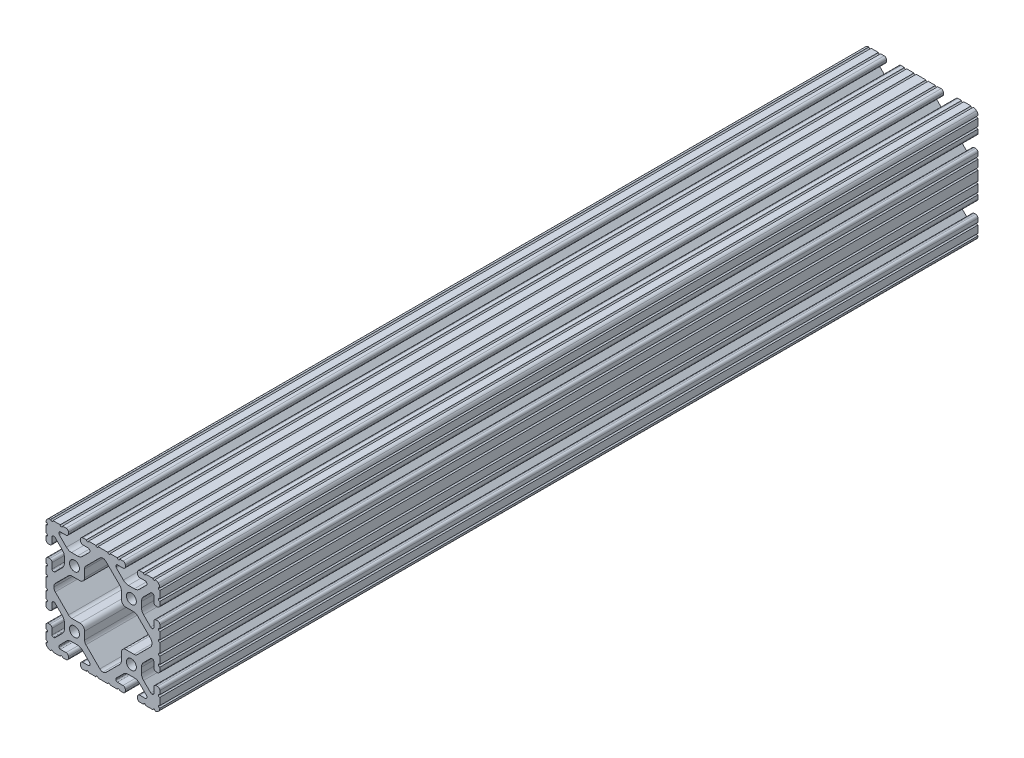
SolidWorks part; units mm, degrees
ref_plane "Front Plane" through (0, 0, 0) normal (0, 0, 1) x (1, 0, 0)
ref_plane "Top Plane" through (0, 0, 0) normal (0, 1, 0) x (1, 0, 0)
ref_plane "Right Plane" through (0, 0, 0) normal (1, 0, 0) x (0, 0, -1)
sketch "Sketch1" plane through (0, 0, 0) normal (0, 0, 1) x (1, 0, 0)
  line L0 (0, 38.1) -> (0, -38.1) construction
  line L1 (-38.1, -38.1) -> (38.1, -38.1) construction
  line L2 (-38.1, -38.1) -> (-38.1, 38.1) construction
  line L3 (-38.1, 38.1) -> (38.1, 38.1) construction
  line L4 (38.1, -38.1) -> (38.1, 38.1) construction
  line L5 (0, 38.1) -> (0, -38.1) construction
  line L6 (-38.1, 0) -> (38.1, 0) construction
  line L7 (-19.05, 19.05) -> (19.05, 19.05) construction
  line L8 (-19.05, 19.05) -> (-19.05, -19.05) construction
  line L9 (-19.05, -19.05) -> (19.05, -19.05) construction
  line L10 (19.05, 19.05) -> (19.05, -19.05) construction
  line L11 (-23.114, 38.1) -> (-23.114, -38.1) construction
  line L12 (-23.114, -38.1) -> (-14.986, 38.1) construction
  line L13 (-14.986, 38.1) -> (-14.986, -38.1) construction
  circle A0 centre (19.05, 19.05) radius 3.3274
  point P0 (0, 0)
  point P9 (0, 0)
  point P12 (-19.05, 0)
  line B0 (-11.3637, -22.8433) -> (-2.0515, -32.1555)
  line B1 (-12.2936, -15.4686) -> (-12.2936, -20.5983)
  line B2 (-20.769, -12.2936) -> (-15.4686, -12.2936)
  line B3 (-31.9021, -2.4756) -> (-23.0141, -11.3637)
  line B4 (-23.0141, 11.3637) -> (-31.9021, 2.4756)
  line B5 (-15.4686, 12.2936) -> (-20.769, 12.2936)
  line B6 (-12.2936, 20.5983) -> (-12.2936, 15.4686)
  line B7 (-2.0515, 32.1555) -> (-11.3637, 22.8433)
  line B8 (11.3637, 22.8433) -> (2.0515, 32.1555)
  line B9 (12.2936, 15.4686) -> (12.2936, 20.5983)
  line B10 (20.769, 12.2936) -> (15.4686, 12.2936)
  line B11 (31.9021, 2.4756) -> (23.0141, 11.3637)
  line B12 (23.0141, -11.3637) -> (31.9021, -2.4756)
  line B13 (15.4686, -12.2936) -> (20.769, -12.2936)
  line B14 (12.2936, -20.5983) -> (12.2936, -15.4686)
  line B15 (2.0515, -32.1555) -> (11.3637, -22.8433)
  line B16 (-4.7773, 38.1) -> (-9.6053, 38.1)
  line B17 (-11.1289, 38.1) -> (-13.4112, 38.1)
  line B18 (-14.986, 36.5252) -> (-14.986, 35.6108)
  line B19 (-13.4112, 34.036) -> (-9.652, 34.036)
  line B20 (-8.763, 33.147) -> (-8.763, 32.4935)
  line B21 (-9.0234, 31.8649) -> (-13.6907, 27.1976)
  line B22 (-17.0493, 25.8064) -> (-21.0507, 25.8064)
  line B23 (-24.4093, 27.1976) -> (-29.1002, 31.8885)
  line B24 (-29.337, 32.7207) -> (-29.337, 33.147)
  line B25 (-28.448, 34.036) -> (-24.6888, 34.036)
  line B26 (-23.114, 35.6108) -> (-23.114, 36.5252)
  line B27 (-24.6888, 38.1) -> (-27.0772, 38.1)
  line B28 (-28.6011, 38.1) -> (-33.4288, 38.1)
  line B29 (-38.1, 33.373) -> (-38.1, 28.5453)
  line B30 (-38.1, 27.0238) -> (-38.1, 24.6302)
  line B31 (-36.5252, 23.0554) -> (-35.6108, 23.0554)
  line B32 (-34.036, 24.6302) -> (-34.036, 28.448)
  line B33 (-33.147, 29.337) -> (-32.6643, 29.337)
  line B34 (-32.0357, 29.0766) -> (-27.1976, 24.2385)
  line B35 (-25.8064, 20.8799) -> (-25.8064, 17.2201)
  line B36 (-27.1976, 13.8615) -> (-31.9489, 9.1101)
  line B37 (-32.7869, 8.763) -> (-33.0603, 8.763)
  line B38 (-34.036, 9.7387) -> (-34.036, 13.4698)
  line B39 (-35.6108, 15.0446) -> (-36.5252, 15.0446)
  line B40 (-38.1, 13.4698) -> (-38.1, 11.075)
  line B41 (-38.1, 9.552) -> (-38.1, 4.7238)
  line B42 (-38.1, 3.2007) -> (-38.1, -3.2007)
  line B43 (-38.1, -4.7238) -> (-38.1, -9.552)
  line B44 (-38.1, -11.075) -> (-38.1, -13.4698)
  line B45 (-36.5252, -15.0446) -> (-35.6108, -15.0446)
  line B46 (-34.036, -13.4698) -> (-34.036, -9.7387)
  line B47 (-33.0603, -8.763) -> (-32.7869, -8.763)
  line B48 (-31.9489, -9.1101) -> (-27.1976, -13.8615)
  line B49 (-25.8064, -17.2201) -> (-25.8064, -20.8799)
  line B50 (-27.1976, -24.2385) -> (-32.0357, -29.0766)
  line B51 (-32.6643, -29.337) -> (-33.147, -29.337)
  line B52 (-34.036, -28.448) -> (-34.036, -24.6302)
  line B53 (-35.6108, -23.0554) -> (-36.5252, -23.0554)
  line B54 (-38.1, -24.6302) -> (-38.1, -27.0238)
  line B55 (-38.1, -28.5453) -> (-38.1, -33.373)
  line B56 (-33.4288, -38.1) -> (-28.6011, -38.1)
  line B57 (-27.0772, -38.1) -> (-24.6888, -38.1)
  line B58 (-23.114, -36.5252) -> (-23.114, -35.6108)
  line B59 (-24.6888, -34.036) -> (-28.448, -34.036)
  line B60 (-29.337, -33.147) -> (-29.337, -32.7207)
  line B61 (-29.1002, -31.8885) -> (-24.4093, -27.1976)
  line B62 (-21.0507, -25.8064) -> (-17.0493, -25.8064)
  line B63 (-13.6907, -27.1976) -> (-9.0234, -31.8649)
  line B64 (-8.763, -32.4935) -> (-8.763, -33.147)
  line B65 (-9.652, -34.036) -> (-13.4112, -34.036)
  line B66 (-14.986, -35.6108) -> (-14.986, -36.5252)
  line B67 (-13.4112, -38.1) -> (-11.1289, -38.1)
  line B68 (-9.6053, -38.1) -> (-4.7773, -38.1)
  line B69 (-3.2537, -38.1) -> (3.2537, -38.1)
  line B70 (4.7773, -38.1) -> (9.6053, -38.1)
  line B71 (11.1289, -38.1) -> (13.4112, -38.1)
  line B72 (14.986, -36.5252) -> (14.986, -35.6108)
  line B73 (13.4112, -34.036) -> (9.652, -34.036)
  line B74 (8.763, -33.147) -> (8.763, -32.4935)
  line B75 (9.0234, -31.8649) -> (13.6907, -27.1976)
  line B76 (17.0493, -25.8064) -> (21.0507, -25.8064)
  line B77 (24.4093, -27.1976) -> (29.1002, -31.8885)
  line B78 (29.337, -32.7207) -> (29.337, -33.147)
  line B79 (28.448, -34.036) -> (24.6888, -34.036)
  line B80 (23.114, -35.6108) -> (23.114, -36.5252)
  line B81 (24.6888, -38.1) -> (27.0772, -38.1)
  line B82 (28.6011, -38.1) -> (33.4288, -38.1)
  line B83 (38.1, -33.373) -> (38.1, -28.5453)
  line B84 (38.1, -27.0238) -> (38.1, -24.6302)
  line B85 (36.5252, -23.0554) -> (35.6108, -23.0554)
  line B86 (34.036, -24.6302) -> (34.036, -28.448)
  line B87 (33.147, -29.337) -> (32.6643, -29.337)
  line B88 (32.0357, -29.0766) -> (27.1976, -24.2385)
  line B89 (25.8064, -20.8799) -> (25.8064, -17.2201)
  line B90 (27.1976, -13.8615) -> (31.9489, -9.1101)
  line B91 (32.7869, -8.763) -> (33.0603, -8.763)
  line B92 (34.036, -9.7387) -> (34.036, -13.4698)
  line B93 (35.6108, -15.0446) -> (36.5252, -15.0446)
  line B94 (38.1, -13.4698) -> (38.1, -11.075)
  line B95 (38.1, -9.552) -> (38.1, -4.7238)
  line B96 (38.1, -3.2007) -> (38.1, 3.2007)
  line B97 (38.1, 4.7238) -> (38.1, 9.552)
  line B98 (38.1, 11.075) -> (38.1, 13.4698)
  line B99 (36.5252, 15.0446) -> (35.6108, 15.0446)
  line B100 (34.036, 13.4698) -> (34.036, 9.7387)
  line B101 (33.0603, 8.763) -> (32.7869, 8.763)
  line B102 (31.9489, 9.1101) -> (27.1976, 13.8615)
  line B103 (25.8064, 17.2201) -> (25.8064, 20.8799)
  line B104 (27.1976, 24.2385) -> (32.0357, 29.0766)
  line B105 (32.6643, 29.337) -> (33.147, 29.337)
  line B106 (34.036, 28.448) -> (34.036, 24.6302)
  line B107 (35.6108, 23.0554) -> (36.5252, 23.0554)
  line B108 (38.1, 24.6302) -> (38.1, 27.0238)
  line B109 (38.1, 28.5453) -> (38.1, 33.373)
  line B110 (33.4288, 38.1) -> (28.6011, 38.1)
  line B111 (27.0772, 38.1) -> (24.6888, 38.1)
  line B112 (23.114, 36.5252) -> (23.114, 35.6108)
  line B113 (24.6888, 34.036) -> (28.448, 34.036)
  line B114 (29.337, 33.147) -> (29.337, 32.7207)
  line B115 (29.1002, 31.8885) -> (24.4093, 27.1976)
  line B116 (21.0507, 25.8064) -> (17.0493, 25.8064)
  line B117 (13.6907, 27.1976) -> (9.0234, 31.8649)
  line B118 (8.763, 32.4935) -> (8.763, 33.147)
  line B119 (9.652, 34.036) -> (13.4112, 34.036)
  line B120 (14.986, 35.6108) -> (14.986, 36.5252)
  line B121 (13.4112, 38.1) -> (11.1289, 38.1)
  line B122 (9.6053, 38.1) -> (4.7773, 38.1)
  line B123 (3.2537, 38.1) -> (-3.2537, 38.1)
  circle B124 centre (-19.05, 19.05) radius 3.3274
  circle B125 centre (-19.05, -19.05) radius 3.3274
  circle B126 centre (19.05, -19.05) radius 3.3274
  circle B127 centre (19.05, 19.05) radius 3.3274
  arc B128 (0, -33.011) -> (2.0515, -32.1555) centre (-0.0139, -30.09) ccw
  arc B129 (-2.0515, -32.1555) -> (0, -33.011) centre (0.0139, -30.09) ccw
  arc B130 (-12.2936, -20.5983) -> (-11.3637, -22.8433) centre (-9.1186, -20.5983) ccw
  arc B131 (-12.2936, -15.4686) -> (-15.4686, -12.2936) centre (-15.4686, -15.4686) ccw
  arc B132 (-23.0141, -11.3637) -> (-20.769, -12.2936) centre (-20.769, -9.1186) ccw
  arc B133 (-32.7287, 0) -> (-31.9021, -2.4756) centre (-29.8367, -0.4102) ccw
  arc B134 (-31.9021, 2.4756) -> (-32.7287, 0) centre (-29.8367, 0.4102) ccw
  arc B135 (-20.769, 12.2936) -> (-23.0141, 11.3637) centre (-20.769, 9.1186) ccw
  arc B136 (-15.4686, 12.2936) -> (-12.2936, 15.4686) centre (-15.4686, 15.4686) ccw
  arc B137 (-11.3637, 22.8433) -> (-12.2936, 20.5983) centre (-9.1186, 20.5983) ccw
  arc B138 (0, 33.011) -> (-2.0515, 32.1555) centre (0.0139, 30.09) ccw
  arc B139 (2.0515, 32.1555) -> (0, 33.011) centre (-0.0139, 30.09) ccw
  arc B140 (12.2936, 20.5983) -> (11.3637, 22.8433) centre (9.1186, 20.5983) ccw
  arc B141 (12.2936, 15.4686) -> (15.4686, 12.2936) centre (15.4686, 15.4686) ccw
  arc B142 (23.0141, 11.3637) -> (20.769, 12.2936) centre (20.769, 9.1186) ccw
  arc B143 (32.7287, 0) -> (31.9021, 2.4756) centre (29.8367, 0.4102) ccw
  arc B144 (31.9021, -2.4756) -> (32.7287, 0) centre (29.8367, -0.4102) ccw
  arc B145 (20.769, -12.2936) -> (23.0141, -11.3637) centre (20.769, -9.1186) ccw
  arc B146 (15.4686, -12.2936) -> (12.2936, -15.4686) centre (15.4686, -15.4686) ccw
  arc B147 (11.3637, -22.8433) -> (12.2936, -20.5983) centre (9.1186, -20.5983) ccw
  arc B148 (-4.7773, 38.1) -> (-3.2537, 38.1) centre (-4.0155, 38.0824) ccw
  arc B149 (-11.1289, 38.1) -> (-9.6053, 38.1) centre (-10.3671, 38.0824) ccw
  arc B150 (-13.4112, 38.1) -> (-14.986, 36.5252) centre (-13.4112, 36.5252) ccw
  arc B151 (-14.986, 35.6108) -> (-13.4112, 34.036) centre (-13.4112, 35.6108) ccw
  arc B152 (-8.763, 33.147) -> (-9.652, 34.036) centre (-9.652, 33.147) ccw
  arc B153 (-9.0234, 31.8649) -> (-8.763, 32.4935) centre (-9.652, 32.4935) ccw
  arc B154 (-17.0493, 25.8064) -> (-13.6907, 27.1976) centre (-17.0493, 30.5562) ccw
  arc B155 (-24.4093, 27.1976) -> (-21.0507, 25.8064) centre (-21.0507, 30.5562) ccw
  arc B156 (-29.337, 32.7207) -> (-29.1002, 31.8885) centre (-28.4716, 32.5172) ccw
  arc B157 (-28.448, 34.036) -> (-29.337, 33.147) centre (-28.448, 33.147) ccw
  arc B158 (-24.6888, 34.036) -> (-23.114, 35.6108) centre (-24.6888, 35.6108) ccw
  arc B159 (-23.114, 36.5252) -> (-24.6888, 38.1) centre (-24.6888, 36.5252) ccw
  arc B160 (-28.6011, 38.1) -> (-27.0772, 38.1) centre (-27.8392, 38.0824) ccw
  arc B161 (-34.9527, 38.1) -> (-33.4288, 38.1) centre (-34.1907, 38.0824) ccw
  arc B162 (-34.9527, 38.1) -> (-37.0861, 37.1826) centre (-34.8521, 34.9266) ccw
  arc B163 (-37.0861, 37.1826) -> (-38.1, 34.8455) centre (-34.925, 34.8566) ccw
  arc B164 (-38.1, 33.373) -> (-38.1, 34.8455) centre (-37.9035, 34.1092) ccw
  arc B165 (-38.1, 27.0238) -> (-38.1, 28.5453) centre (-37.9035, 27.7845) ccw
  arc B166 (-38.1, 24.6302) -> (-36.5252, 23.0554) centre (-36.5252, 24.6302) ccw
  arc B167 (-35.6108, 23.0554) -> (-34.036, 24.6302) centre (-35.6108, 24.6302) ccw
  arc B168 (-33.147, 29.337) -> (-34.036, 28.448) centre (-33.147, 28.448) ccw
  arc B169 (-32.0357, 29.0766) -> (-32.6643, 29.337) centre (-32.6643, 28.448) ccw
  arc B170 (-25.8064, 20.8799) -> (-27.1976, 24.2385) centre (-30.5562, 20.8799) ccw
  arc B171 (-27.1976, 13.8615) -> (-25.8064, 17.2201) centre (-30.5562, 17.2201) ccw
  arc B172 (-32.7869, 8.763) -> (-31.9489, 9.1101) centre (-32.7869, 9.9481) ccw
  arc B173 (-34.036, 9.7387) -> (-33.0603, 8.763) centre (-33.0603, 9.7387) ccw
  arc B174 (-34.036, 13.4698) -> (-35.6108, 15.0446) centre (-35.6108, 13.4698) ccw
  arc B175 (-36.5252, 15.0446) -> (-38.1, 13.4698) centre (-36.5252, 13.4698) ccw
  arc B176 (-38.1, 9.552) -> (-38.1, 11.075) centre (-37.9035, 10.3135) ccw
  arc B177 (-38.1, 3.2007) -> (-38.1, 4.7238) centre (-37.9035, 3.9622) ccw
  arc B178 (-38.1, -4.7238) -> (-38.1, -3.2007) centre (-37.9035, -3.9622) ccw
  arc B179 (-38.1, -11.075) -> (-38.1, -9.552) centre (-37.9035, -10.3135) ccw
  arc B180 (-38.1, -13.4698) -> (-36.5252, -15.0446) centre (-36.5252, -13.4698) ccw
  arc B181 (-35.6108, -15.0446) -> (-34.036, -13.4698) centre (-35.6108, -13.4698) ccw
  arc B182 (-33.0603, -8.763) -> (-34.036, -9.7387) centre (-33.0603, -9.7387) ccw
  arc B183 (-31.9489, -9.1101) -> (-32.7869, -8.763) centre (-32.7869, -9.9481) ccw
  arc B184 (-25.8064, -17.2201) -> (-27.1976, -13.8615) centre (-30.5562, -17.2201) ccw
  arc B185 (-27.1976, -24.2385) -> (-25.8064, -20.8799) centre (-30.5562, -20.8799) ccw
  arc B186 (-32.6643, -29.337) -> (-32.0357, -29.0766) centre (-32.6643, -28.448) ccw
  arc B187 (-34.036, -28.448) -> (-33.147, -29.337) centre (-33.147, -28.448) ccw
  arc B188 (-34.036, -24.6302) -> (-35.6108, -23.0554) centre (-35.6108, -24.6302) ccw
  arc B189 (-36.5252, -23.0554) -> (-38.1, -24.6302) centre (-36.5252, -24.6302) ccw
  arc B190 (-38.1, -28.5453) -> (-38.1, -27.0238) centre (-37.9035, -27.7845) ccw
  arc B191 (-38.1, -34.8455) -> (-38.1, -33.373) centre (-37.9035, -34.1092) ccw
  arc B192 (-38.1, -34.8455) -> (-37.0861, -37.1826) centre (-34.925, -34.8566) ccw
  arc B193 (-37.0861, -37.1826) -> (-34.9527, -38.1) centre (-34.8521, -34.9266) ccw
  arc B194 (-33.4288, -38.1) -> (-34.9527, -38.1) centre (-34.1907, -38.0824) ccw
  arc B195 (-27.0772, -38.1) -> (-28.6011, -38.1) centre (-27.8392, -38.0824) ccw
  arc B196 (-24.6888, -38.1) -> (-23.114, -36.5252) centre (-24.6888, -36.5252) ccw
  arc B197 (-23.114, -35.6108) -> (-24.6888, -34.036) centre (-24.6888, -35.6108) ccw
  arc B198 (-29.337, -33.147) -> (-28.448, -34.036) centre (-28.448, -33.147) ccw
  arc B199 (-29.1002, -31.8885) -> (-29.337, -32.7207) centre (-28.4716, -32.5172) ccw
  arc B200 (-21.0507, -25.8064) -> (-24.4093, -27.1976) centre (-21.0507, -30.5562) ccw
  arc B201 (-13.6907, -27.1976) -> (-17.0493, -25.8064) centre (-17.0493, -30.5562) ccw
  arc B202 (-8.763, -32.4935) -> (-9.0234, -31.8649) centre (-9.652, -32.4935) ccw
  arc B203 (-9.652, -34.036) -> (-8.763, -33.147) centre (-9.652, -33.147) ccw
  arc B204 (-13.4112, -34.036) -> (-14.986, -35.6108) centre (-13.4112, -35.6108) ccw
  arc B205 (-14.986, -36.5252) -> (-13.4112, -38.1) centre (-13.4112, -36.5252) ccw
  arc B206 (-9.6053, -38.1) -> (-11.1289, -38.1) centre (-10.3671, -38.0824) ccw
  arc B207 (-3.2537, -38.1) -> (-4.7773, -38.1) centre (-4.0155, -38.0824) ccw
  arc B208 (4.7773, -38.1) -> (3.2537, -38.1) centre (4.0155, -38.0824) ccw
  arc B209 (11.1289, -38.1) -> (9.6053, -38.1) centre (10.3671, -38.0824) ccw
  arc B210 (13.4112, -38.1) -> (14.986, -36.5252) centre (13.4112, -36.5252) ccw
  arc B211 (14.986, -35.6108) -> (13.4112, -34.036) centre (13.4112, -35.6108) ccw
  arc B212 (8.763, -33.147) -> (9.652, -34.036) centre (9.652, -33.147) ccw
  arc B213 (9.0234, -31.8649) -> (8.763, -32.4935) centre (9.652, -32.4935) ccw
  arc B214 (17.0493, -25.8064) -> (13.6907, -27.1976) centre (17.0493, -30.5562) ccw
  arc B215 (24.4093, -27.1976) -> (21.0507, -25.8064) centre (21.0507, -30.5562) ccw
  arc B216 (29.337, -32.7207) -> (29.1002, -31.8885) centre (28.4716, -32.5172) ccw
  arc B217 (28.448, -34.036) -> (29.337, -33.147) centre (28.448, -33.147) ccw
  arc B218 (24.6888, -34.036) -> (23.114, -35.6108) centre (24.6888, -35.6108) ccw
  arc B219 (23.114, -36.5252) -> (24.6888, -38.1) centre (24.6888, -36.5252) ccw
  arc B220 (28.6011, -38.1) -> (27.0772, -38.1) centre (27.8392, -38.0824) ccw
  arc B221 (34.9527, -38.1) -> (33.4288, -38.1) centre (34.1907, -38.0824) ccw
  arc B222 (34.9527, -38.1) -> (37.0861, -37.1826) centre (34.8521, -34.9266) ccw
  arc B223 (37.0861, -37.1826) -> (38.1, -34.8455) centre (34.925, -34.8566) ccw
  arc B224 (38.1, -33.373) -> (38.1, -34.8455) centre (37.9035, -34.1092) ccw
  arc B225 (38.1, -27.0238) -> (38.1, -28.5453) centre (37.9035, -27.7845) ccw
  arc B226 (38.1, -24.6302) -> (36.5252, -23.0554) centre (36.5252, -24.6302) ccw
  arc B227 (35.6108, -23.0554) -> (34.036, -24.6302) centre (35.6108, -24.6302) ccw
  arc B228 (33.147, -29.337) -> (34.036, -28.448) centre (33.147, -28.448) ccw
  arc B229 (32.0357, -29.0766) -> (32.6643, -29.337) centre (32.6643, -28.448) ccw
  arc B230 (25.8064, -20.8799) -> (27.1976, -24.2385) centre (30.5562, -20.8799) ccw
  arc B231 (27.1976, -13.8615) -> (25.8064, -17.2201) centre (30.5562, -17.2201) ccw
  arc B232 (32.7869, -8.763) -> (31.9489, -9.1101) centre (32.7869, -9.9481) ccw
  arc B233 (34.036, -9.7387) -> (33.0603, -8.763) centre (33.0603, -9.7387) ccw
  arc B234 (34.036, -13.4698) -> (35.6108, -15.0446) centre (35.6108, -13.4698) ccw
  arc B235 (36.5252, -15.0446) -> (38.1, -13.4698) centre (36.5252, -13.4698) ccw
  arc B236 (38.1, -9.552) -> (38.1, -11.075) centre (37.9035, -10.3135) ccw
  arc B237 (38.1, -3.2007) -> (38.1, -4.7238) centre (37.9035, -3.9622) ccw
  arc B238 (38.1, 4.7238) -> (38.1, 3.2007) centre (37.9035, 3.9622) ccw
  arc B239 (38.1, 11.075) -> (38.1, 9.552) centre (37.9035, 10.3135) ccw
  arc B240 (38.1, 13.4698) -> (36.5252, 15.0446) centre (36.5252, 13.4698) ccw
  arc B241 (35.6108, 15.0446) -> (34.036, 13.4698) centre (35.6108, 13.4698) ccw
  arc B242 (33.0603, 8.763) -> (34.036, 9.7387) centre (33.0603, 9.7387) ccw
  arc B243 (31.9489, 9.1101) -> (32.7869, 8.763) centre (32.7869, 9.9481) ccw
  arc B244 (25.8064, 17.2201) -> (27.1976, 13.8615) centre (30.5562, 17.2201) ccw
  arc B245 (27.1976, 24.2385) -> (25.8064, 20.8799) centre (30.5562, 20.8799) ccw
  arc B246 (32.6643, 29.337) -> (32.0357, 29.0766) centre (32.6643, 28.448) ccw
  arc B247 (34.036, 28.448) -> (33.147, 29.337) centre (33.147, 28.448) ccw
  arc B248 (34.036, 24.6302) -> (35.6108, 23.0554) centre (35.6108, 24.6302) ccw
  arc B249 (36.5252, 23.0554) -> (38.1, 24.6302) centre (36.5252, 24.6302) ccw
  arc B250 (38.1, 28.5453) -> (38.1, 27.0238) centre (37.9035, 27.7845) ccw
  arc B251 (38.1, 34.8455) -> (38.1, 33.373) centre (37.9035, 34.1092) ccw
  arc B252 (38.1, 34.8455) -> (37.0861, 37.1826) centre (34.925, 34.8566) ccw
  arc B253 (37.0861, 37.1826) -> (34.9527, 38.1) centre (34.8521, 34.9266) ccw
  arc B254 (33.4288, 38.1) -> (34.9527, 38.1) centre (34.1907, 38.0824) ccw
  arc B255 (27.0772, 38.1) -> (28.6011, 38.1) centre (27.8392, 38.0824) ccw
  arc B256 (24.6888, 38.1) -> (23.114, 36.5252) centre (24.6888, 36.5252) ccw
  arc B257 (23.114, 35.6108) -> (24.6888, 34.036) centre (24.6888, 35.6108) ccw
  arc B258 (29.337, 33.147) -> (28.448, 34.036) centre (28.448, 33.147) ccw
  arc B259 (29.1002, 31.8885) -> (29.337, 32.7207) centre (28.4716, 32.5172) ccw
  arc B260 (21.0507, 25.8064) -> (24.4093, 27.1976) centre (21.0507, 30.5562) ccw
  arc B261 (13.6907, 27.1976) -> (17.0493, 25.8064) centre (17.0493, 30.5562) ccw
  arc B262 (8.763, 32.4935) -> (9.0234, 31.8649) centre (9.652, 32.4935) ccw
  arc B263 (9.652, 34.036) -> (8.763, 33.147) centre (9.652, 33.147) ccw
  arc B264 (13.4112, 34.036) -> (14.986, 35.6108) centre (13.4112, 35.6108) ccw
  arc B265 (14.986, 36.5252) -> (13.4112, 38.1) centre (13.4112, 36.5252) ccw
  arc B266 (9.6053, 38.1) -> (11.1289, 38.1) centre (10.3671, 38.0824) ccw
  arc B267 (3.2537, 38.1) -> (4.7773, 38.1) centre (4.0155, 38.0824) ccw
  dimension "Center Hole Diameter" = 6.6548
  dimension "Rail Width" = 76.2
  dimension "Rail Height" = 76.2
  dimension "T-Slot Width" = 8.128
sketch_block_instance "Block1-1"
sketch_block "Block1"
sketch "Sketch2" plane through (0, 0, 0) normal (1, 0, 0) x (0, 0, -1)
  line L0 (-273.8, 0) -> (273.8, 0) construction
  line L1 (-273.8, 38.1) -> (-273.8, -38.1) construction
  line L2 (-273.8, -38.1) -> (273.8, -38.1) construction
  line L3 (273.8, -38.1) -> (273.8, 38.1) construction
  line L4 (-172.2, 0) -> (-172.2, 38.1) construction
  line L5 (-172.2, 38.1) -> (172.2, 38.1) construction
  line L6 (172.2, 38.1) -> (172.2, 0) construction
  point P5 (172.2, 0)
  point P10 (-172.2, 0)
  dimension "D1" = 101.6
  dimension "Length" = 547.6
  dimension "D2" = 101.6
sketch "Sketch3" plane through (0, 0, 0) normal (0, 0, 1) x (1, 0, 0)
  line L0 (-11.3637, -22.8433) -> (-2.0515, -32.1555) construction
  line L1 (-12.2936, -15.4686) -> (-12.2936, -20.5983) construction
  line L2 (-20.769, -12.2936) -> (-15.4686, -12.2936) construction
  line L3 (-31.9021, -2.4756) -> (-23.0141, -11.3637) construction
  line L4 (-23.0141, 11.3637) -> (-31.9021, 2.4756) construction
  line L5 (-15.4686, 12.2936) -> (-20.769, 12.2936) construction
  line L6 (-12.2936, 20.5983) -> (-12.2936, 15.4686) construction
  line L7 (-2.0515, 32.1555) -> (-11.3637, 22.8433) construction
  line L8 (11.3637, 22.8433) -> (2.0515, 32.1555) construction
  line L9 (12.2936, 15.4686) -> (12.2936, 20.5983) construction
  line L10 (20.769, 12.2936) -> (15.4686, 12.2936) construction
  line L11 (31.9021, 2.4756) -> (23.0141, 11.3637) construction
  line L12 (23.0141, -11.3637) -> (31.9021, -2.4756) construction
  line L13 (15.4686, -12.2936) -> (20.769, -12.2936) construction
  line L14 (12.2936, -20.5983) -> (12.2936, -15.4686) construction
  line L15 (2.0515, -32.1555) -> (11.3637, -22.8433) construction
  line L16 (34.036, 28.448) -> (34.036, 24.6302) construction
  line L17 (35.6108, 23.0554) -> (36.5252, 23.0554) construction
  line L18 (38.1, 24.6302) -> (38.1, 27.0238) construction
  line L19 (38.1, 28.5453) -> (38.1, 33.373) construction
  line L20 (33.4288, 38.1) -> (28.6011, 38.1) construction
  line L21 (27.0772, 38.1) -> (24.6888, 38.1) construction
  line L22 (23.114, 36.5252) -> (23.114, 35.6108) construction
  line L23 (24.6888, 34.036) -> (28.448, 34.036) construction
  line L24 (29.337, 33.147) -> (29.337, 32.7207) construction
  line L25 (29.1002, 31.8885) -> (24.4093, 27.1976) construction
  line L26 (21.0507, 25.8064) -> (17.0493, 25.8064) construction
  line L27 (13.6907, 27.1976) -> (9.0234, 31.8649) construction
  line L28 (8.763, 32.4935) -> (8.763, 33.147) construction
  line L29 (9.652, 34.036) -> (13.4112, 34.036) construction
  line L30 (14.986, 35.6108) -> (14.986, 36.5252) construction
  line L31 (13.4112, 38.1) -> (11.1289, 38.1) construction
  line L32 (9.6053, 38.1) -> (4.7773, 38.1) construction
  line L33 (3.2537, 38.1) -> (-3.2537, 38.1) construction
  line L34 (-4.7773, 38.1) -> (-9.6053, 38.1) construction
  line L35 (-11.1289, 38.1) -> (-13.4112, 38.1) construction
  line L36 (-14.986, 36.5252) -> (-14.986, 35.6108) construction
  line L37 (-13.4112, 34.036) -> (-9.652, 34.036) construction
  line L38 (-8.763, 33.147) -> (-8.763, 32.4935) construction
  line L39 (-9.0234, 31.8649) -> (-13.6907, 27.1976) construction
  line L40 (-17.0493, 25.8064) -> (-21.0507, 25.8064) construction
  line L41 (-24.4093, 27.1976) -> (-29.1002, 31.8885) construction
  line L42 (-29.337, 32.7207) -> (-29.337, 33.147) construction
  line L43 (-28.448, 34.036) -> (-24.6888, 34.036) construction
  line L44 (-23.114, 35.6108) -> (-23.114, 36.5252) construction
  line L45 (-24.6888, 38.1) -> (-27.0772, 38.1) construction
  line L46 (-28.6011, 38.1) -> (-33.4288, 38.1) construction
  line L47 (-38.1, 33.373) -> (-38.1, 28.5453) construction
  line L48 (-38.1, 27.0238) -> (-38.1, 24.6302) construction
  line L49 (-36.5252, 23.0554) -> (-35.6108, 23.0554) construction
  line L50 (-34.036, 24.6302) -> (-34.036, 28.448) construction
  line L51 (-33.147, 29.337) -> (-32.6643, 29.337) construction
  line L52 (-32.0357, 29.0766) -> (-27.1976, 24.2385) construction
  line L53 (-25.8064, 20.8799) -> (-25.8064, 17.2201) construction
  line L54 (-27.1976, 13.8615) -> (-31.9489, 9.1101) construction
  line L55 (-32.7869, 8.763) -> (-33.0603, 8.763) construction
  line L56 (-34.036, 9.7387) -> (-34.036, 13.4698) construction
  line L57 (-35.6108, 15.0446) -> (-36.5252, 15.0446) construction
  line L58 (-38.1, 13.4698) -> (-38.1, 11.075) construction
  line L59 (-38.1, 9.552) -> (-38.1, 4.7238) construction
  line L60 (-38.1, 3.2007) -> (-38.1, -3.2007) construction
  line L61 (-38.1, -4.7238) -> (-38.1, -9.552) construction
  line L62 (-38.1, -11.075) -> (-38.1, -13.4698) construction
  line L63 (-36.5252, -15.0446) -> (-35.6108, -15.0446) construction
  line L64 (-34.036, -13.4698) -> (-34.036, -9.7387) construction
  line L65 (-33.0603, -8.763) -> (-32.7869, -8.763) construction
  line L66 (-31.9489, -9.1101) -> (-27.1976, -13.8615) construction
  line L67 (-25.8064, -17.2201) -> (-25.8064, -20.8799) construction
  line L68 (-27.1976, -24.2385) -> (-32.0357, -29.0766) construction
  line L69 (-32.6643, -29.337) -> (-33.147, -29.337) construction
  line L70 (-34.036, -28.448) -> (-34.036, -24.6302) construction
  line L71 (-35.6108, -23.0554) -> (-36.5252, -23.0554) construction
  line L72 (-38.1, -24.6302) -> (-38.1, -27.0238) construction
  line L73 (-38.1, -28.5453) -> (-38.1, -33.373) construction
  line L74 (-33.4288, -38.1) -> (-28.6011, -38.1) construction
  line L75 (-27.0772, -38.1) -> (-24.6888, -38.1) construction
  line L76 (-23.114, -36.5252) -> (-23.114, -35.6108) construction
  line L77 (-24.6888, -34.036) -> (-28.448, -34.036) construction
  line L78 (-29.337, -33.147) -> (-29.337, -32.7207) construction
  line L79 (-29.1002, -31.8885) -> (-24.4093, -27.1976) construction
  line L80 (-21.0507, -25.8064) -> (-17.0493, -25.8064) construction
  line L81 (-13.6907, -27.1976) -> (-9.0234, -31.8649) construction
  line L82 (-8.763, -32.4935) -> (-8.763, -33.147) construction
  line L83 (-9.652, -34.036) -> (-13.4112, -34.036) construction
  line L84 (-14.986, -35.6108) -> (-14.986, -36.5252) construction
  line L85 (-13.4112, -38.1) -> (-11.1289, -38.1) construction
  line L86 (-9.6053, -38.1) -> (-4.7773, -38.1) construction
  line L87 (-3.2537, -38.1) -> (3.2537, -38.1) construction
  line L88 (4.7773, -38.1) -> (9.6053, -38.1) construction
  line L89 (11.1289, -38.1) -> (13.4112, -38.1) construction
  line L90 (14.986, -36.5252) -> (14.986, -35.6108) construction
  line L91 (13.4112, -34.036) -> (9.652, -34.036) construction
  line L92 (8.763, -33.147) -> (8.763, -32.4935) construction
  line L93 (9.0234, -31.8649) -> (13.6907, -27.1976) construction
  line L94 (17.0493, -25.8064) -> (21.0507, -25.8064) construction
  line L95 (24.4093, -27.1976) -> (29.1002, -31.8885) construction
  line L96 (29.337, -32.7207) -> (29.337, -33.147) construction
  line L97 (28.448, -34.036) -> (24.6888, -34.036) construction
  line L98 (23.114, -35.6108) -> (23.114, -36.5252) construction
  line L99 (24.6888, -38.1) -> (27.0772, -38.1) construction
  line L100 (28.6011, -38.1) -> (33.4288, -38.1) construction
  line L101 (38.1, -33.373) -> (38.1, -28.5453) construction
  line L102 (38.1, -27.0238) -> (38.1, -24.6302) construction
  line L103 (36.5252, -23.0554) -> (35.6108, -23.0554) construction
  line L104 (34.036, -24.6302) -> (34.036, -28.448) construction
  line L105 (33.147, -29.337) -> (32.6643, -29.337) construction
  line L106 (32.0357, -29.0766) -> (27.1976, -24.2385) construction
  line L107 (25.8064, -20.8799) -> (25.8064, -17.2201) construction
  line L108 (27.1976, -13.8615) -> (31.9489, -9.1101) construction
  line L109 (32.7869, -8.763) -> (33.0603, -8.763) construction
  line L110 (34.036, -9.7387) -> (34.036, -13.4698) construction
  line L111 (35.6108, -15.0446) -> (36.5252, -15.0446) construction
  line L112 (38.1, -13.4698) -> (38.1, -11.075) construction
  line L113 (38.1, -9.552) -> (38.1, -4.7238) construction
  line L114 (38.1, -3.2007) -> (38.1, 3.2007) construction
  line L115 (38.1, 4.7238) -> (38.1, 9.552) construction
  line L116 (38.1, 11.075) -> (38.1, 13.4698) construction
  line L117 (36.5252, 15.0446) -> (35.6108, 15.0446) construction
  line L118 (34.036, 13.4698) -> (34.036, 9.7387) construction
  line L119 (33.0603, 8.763) -> (32.7869, 8.763) construction
  line L120 (31.9489, 9.1101) -> (27.1976, 13.8615) construction
  line L121 (25.8064, 17.2201) -> (25.8064, 20.8799) construction
  line L122 (27.1976, 24.2385) -> (32.0357, 29.0766) construction
  line L123 (32.6643, 29.337) -> (33.147, 29.337) construction
  line L124 (-11.3637, -22.8433) -> (-2.0515, -32.1555)
  line L125 (-12.2936, -15.4686) -> (-12.2936, -20.5983)
  line L126 (-20.769, -12.2936) -> (-15.4686, -12.2936)
  line L127 (-31.9021, -2.4756) -> (-23.0141, -11.3637)
  line L128 (-23.0141, 11.3637) -> (-31.9021, 2.4756)
  line L129 (-15.4686, 12.2936) -> (-20.769, 12.2936)
  line L130 (-12.2936, 20.5983) -> (-12.2936, 15.4686)
  line L131 (-2.0515, 32.1555) -> (-11.3637, 22.8433)
  line L132 (11.3637, 22.8433) -> (2.0515, 32.1555)
  line L133 (12.2936, 15.4686) -> (12.2936, 20.5983)
  line L134 (20.769, 12.2936) -> (15.4686, 12.2936)
  line L135 (31.9021, 2.4756) -> (23.0141, 11.3637)
  line L136 (23.0141, -11.3637) -> (31.9021, -2.4756)
  line L137 (15.4686, -12.2936) -> (20.769, -12.2936)
  line L138 (12.2936, -20.5983) -> (12.2936, -15.4686)
  line L139 (2.0515, -32.1555) -> (11.3637, -22.8433)
  line L140 (34.036, 28.448) -> (34.036, 24.6302)
  line L141 (35.6108, 23.0554) -> (36.5252, 23.0554)
  line L142 (38.1, 24.6302) -> (38.1, 27.0238)
  line L143 (38.1, 28.5453) -> (38.1, 33.373)
  line L144 (33.4288, 38.1) -> (28.6011, 38.1)
  line L145 (27.0772, 38.1) -> (24.6888, 38.1)
  line L146 (23.114, 36.5252) -> (23.114, 35.6108)
  line L147 (24.6888, 34.036) -> (28.448, 34.036)
  line L148 (29.337, 33.147) -> (29.337, 32.7207)
  line L149 (29.1002, 31.8885) -> (24.4093, 27.1976)
  line L150 (21.0507, 25.8064) -> (17.0493, 25.8064)
  line L151 (13.6907, 27.1976) -> (9.0234, 31.8649)
  line L152 (8.763, 32.4935) -> (8.763, 33.147)
  line L153 (9.652, 34.036) -> (13.4112, 34.036)
  line L154 (14.986, 35.6108) -> (14.986, 36.5252)
  line L155 (13.4112, 38.1) -> (11.1289, 38.1)
  line L156 (9.6053, 38.1) -> (4.7773, 38.1)
  line L157 (3.2537, 38.1) -> (-3.2537, 38.1)
  line L158 (-4.7773, 38.1) -> (-9.6053, 38.1)
  line L159 (-11.1289, 38.1) -> (-13.4112, 38.1)
  line L160 (-14.986, 36.5252) -> (-14.986, 35.6108)
  line L161 (-13.4112, 34.036) -> (-9.652, 34.036)
  line L162 (-8.763, 33.147) -> (-8.763, 32.4935)
  line L163 (-9.0234, 31.8649) -> (-13.6907, 27.1976)
  line L164 (-17.0493, 25.8064) -> (-21.0507, 25.8064)
  line L165 (-24.4093, 27.1976) -> (-29.1002, 31.8885)
  line L166 (-29.337, 32.7207) -> (-29.337, 33.147)
  line L167 (-28.448, 34.036) -> (-24.6888, 34.036)
  line L168 (-23.114, 35.6108) -> (-23.114, 36.5252)
  line L169 (-24.6888, 38.1) -> (-27.0772, 38.1)
  line L170 (-28.6011, 38.1) -> (-33.4288, 38.1)
  line L171 (-38.1, 33.373) -> (-38.1, 28.5453)
  line L172 (-38.1, 27.0238) -> (-38.1, 24.6302)
  line L173 (-36.5252, 23.0554) -> (-35.6108, 23.0554)
  line L174 (-34.036, 24.6302) -> (-34.036, 28.448)
  line L175 (-33.147, 29.337) -> (-32.6643, 29.337)
  line L176 (-32.0357, 29.0766) -> (-27.1976, 24.2385)
  line L177 (-25.8064, 20.8799) -> (-25.8064, 17.2201)
  line L178 (-27.1976, 13.8615) -> (-31.9489, 9.1101)
  line L179 (-32.7869, 8.763) -> (-33.0603, 8.763)
  line L180 (-34.036, 9.7387) -> (-34.036, 13.4698)
  line L181 (-35.6108, 15.0446) -> (-36.5252, 15.0446)
  line L182 (-38.1, 13.4698) -> (-38.1, 11.075)
  line L183 (-38.1, 9.552) -> (-38.1, 4.7238)
  line L184 (-38.1, 3.2007) -> (-38.1, -3.2007)
  line L185 (-38.1, -4.7238) -> (-38.1, -9.552)
  line L186 (-38.1, -11.075) -> (-38.1, -13.4698)
  line L187 (-36.5252, -15.0446) -> (-35.6108, -15.0446)
  line L188 (-34.036, -13.4698) -> (-34.036, -9.7387)
  line L189 (-33.0603, -8.763) -> (-32.7869, -8.763)
  line L190 (-31.9489, -9.1101) -> (-27.1976, -13.8615)
  line L191 (-25.8064, -17.2201) -> (-25.8064, -20.8799)
  line L192 (-27.1976, -24.2385) -> (-32.0357, -29.0766)
  line L193 (-32.6643, -29.337) -> (-33.147, -29.337)
  line L194 (-34.036, -28.448) -> (-34.036, -24.6302)
  line L195 (-35.6108, -23.0554) -> (-36.5252, -23.0554)
  line L196 (-38.1, -24.6302) -> (-38.1, -27.0238)
  line L197 (-38.1, -28.5453) -> (-38.1, -33.373)
  line L198 (-33.4288, -38.1) -> (-28.6011, -38.1)
  line L199 (-27.0772, -38.1) -> (-24.6888, -38.1)
  line L200 (-23.114, -36.5252) -> (-23.114, -35.6108)
  line L201 (-24.6888, -34.036) -> (-28.448, -34.036)
  line L202 (-29.337, -33.147) -> (-29.337, -32.7207)
  line L203 (-29.1002, -31.8885) -> (-24.4093, -27.1976)
  line L204 (-21.0507, -25.8064) -> (-17.0493, -25.8064)
  line L205 (-13.6907, -27.1976) -> (-9.0234, -31.8649)
  line L206 (-8.763, -32.4935) -> (-8.763, -33.147)
  line L207 (-9.652, -34.036) -> (-13.4112, -34.036)
  line L208 (-14.986, -35.6108) -> (-14.986, -36.5252)
  line L209 (-13.4112, -38.1) -> (-11.1289, -38.1)
  line L210 (-9.6053, -38.1) -> (-4.7773, -38.1)
  line L211 (-3.2537, -38.1) -> (3.2537, -38.1)
  line L212 (4.7773, -38.1) -> (9.6053, -38.1)
  line L213 (11.1289, -38.1) -> (13.4112, -38.1)
  line L214 (14.986, -36.5252) -> (14.986, -35.6108)
  line L215 (13.4112, -34.036) -> (9.652, -34.036)
  line L216 (8.763, -33.147) -> (8.763, -32.4935)
  line L217 (9.0234, -31.8649) -> (13.6907, -27.1976)
  line L218 (17.0493, -25.8064) -> (21.0507, -25.8064)
  line L219 (24.4093, -27.1976) -> (29.1002, -31.8885)
  line L220 (29.337, -32.7207) -> (29.337, -33.147)
  line L221 (28.448, -34.036) -> (24.6888, -34.036)
  line L222 (23.114, -35.6108) -> (23.114, -36.5252)
  line L223 (24.6888, -38.1) -> (27.0772, -38.1)
  line L224 (28.6011, -38.1) -> (33.4288, -38.1)
  line L225 (38.1, -33.373) -> (38.1, -28.5453)
  line L226 (38.1, -27.0238) -> (38.1, -24.6302)
  line L227 (36.5252, -23.0554) -> (35.6108, -23.0554)
  line L228 (34.036, -24.6302) -> (34.036, -28.448)
  line L229 (33.147, -29.337) -> (32.6643, -29.337)
  line L230 (32.0357, -29.0766) -> (27.1976, -24.2385)
  line L231 (25.8064, -20.8799) -> (25.8064, -17.2201)
  line L232 (27.1976, -13.8615) -> (31.9489, -9.1101)
  line L233 (32.7869, -8.763) -> (33.0603, -8.763)
  line L234 (34.036, -9.7387) -> (34.036, -13.4698)
  line L235 (35.6108, -15.0446) -> (36.5252, -15.0446)
  line L236 (38.1, -13.4698) -> (38.1, -11.075)
  line L237 (38.1, -9.552) -> (38.1, -4.7238)
  line L238 (38.1, -3.2007) -> (38.1, 3.2007)
  line L239 (38.1, 4.7238) -> (38.1, 9.552)
  line L240 (38.1, 11.075) -> (38.1, 13.4698)
  line L241 (36.5252, 15.0446) -> (35.6108, 15.0446)
  line L242 (34.036, 13.4698) -> (34.036, 9.7387)
  line L243 (33.0603, 8.763) -> (32.7869, 8.763)
  line L244 (31.9489, 9.1101) -> (27.1976, 13.8615)
  line L245 (25.8064, 17.2201) -> (25.8064, 20.8799)
  line L246 (27.1976, 24.2385) -> (32.0357, 29.0766)
  line L247 (32.6643, 29.337) -> (33.147, 29.337)
  arc A0 (-2.0515, -32.1555) -> (0, -33.011) centre (0.0139, -30.09) ccw construction
  circle A1 centre (19.05, 19.05) radius 3.3274
  circle A2 centre (19.05, 19.05) radius 3.3274
  arc A3 (-12.2936, -20.5983) -> (-11.3637, -22.8433) centre (-9.1186, -20.5983) ccw construction
  arc A4 (-12.2936, -15.4686) -> (-15.4686, -12.2936) centre (-15.4686, -15.4686) ccw construction
  arc A5 (-23.0141, -11.3637) -> (-20.769, -12.2936) centre (-20.769, -9.1186) ccw construction
  arc A6 (-32.7287, 0) -> (-31.9021, -2.4756) centre (-29.8367, -0.4102) ccw construction
  arc A7 (-31.9021, 2.4756) -> (-32.7287, 0) centre (-29.8367, 0.4102) ccw construction
  arc A8 (-20.769, 12.2936) -> (-23.0141, 11.3637) centre (-20.769, 9.1186) ccw construction
  arc A9 (-15.4686, 12.2936) -> (-12.2936, 15.4686) centre (-15.4686, 15.4686) ccw construction
  arc A10 (-11.3637, 22.8433) -> (-12.2936, 20.5983) centre (-9.1186, 20.5983) ccw construction
  arc A11 (0, 33.011) -> (-2.0515, 32.1555) centre (0.0139, 30.09) ccw construction
  arc A12 (2.0515, 32.1555) -> (0, 33.011) centre (-0.0139, 30.09) ccw construction
  arc A13 (12.2936, 20.5983) -> (11.3637, 22.8433) centre (9.1186, 20.5983) ccw construction
  arc A14 (12.2936, 15.4686) -> (15.4686, 12.2936) centre (15.4686, 15.4686) ccw construction
  arc A15 (23.0141, 11.3637) -> (20.769, 12.2936) centre (20.769, 9.1186) ccw construction
  arc A16 (32.7287, 0) -> (31.9021, 2.4756) centre (29.8367, 0.4102) ccw construction
  arc A17 (31.9021, -2.4756) -> (32.7287, 0) centre (29.8367, -0.4102) ccw construction
  arc A18 (20.769, -12.2936) -> (23.0141, -11.3637) centre (20.769, -9.1186) ccw construction
  arc A19 (15.4686, -12.2936) -> (12.2936, -15.4686) centre (15.4686, -15.4686) ccw construction
  arc A20 (11.3637, -22.8433) -> (12.2936, -20.5983) centre (9.1186, -20.5983) ccw construction
  arc A21 (0, -33.011) -> (2.0515, -32.1555) centre (-0.0139, -30.09) ccw construction
  circle A22 centre (-19.05, 19.05) radius 3.3274 construction
  circle A23 centre (19.05, -19.05) radius 3.3274 construction
  circle A24 centre (-19.05, -19.05) radius 3.3274 construction
  circle A25 centre (19.05, 19.05) radius 3.3274 construction
  arc A26 (34.036, 24.6302) -> (35.6108, 23.0554) centre (35.6108, 24.6302) ccw construction
  arc A27 (36.5252, 23.0554) -> (38.1, 24.6302) centre (36.5252, 24.6302) ccw construction
  arc A28 (38.1, 28.5453) -> (38.1, 27.0238) centre (37.9035, 27.7845) ccw construction
  arc A29 (38.1, 34.8455) -> (38.1, 33.373) centre (37.9035, 34.1092) ccw construction
  arc A30 (38.1, 34.8455) -> (37.0861, 37.1826) centre (34.925, 34.8566) ccw construction
  arc A31 (37.0861, 37.1826) -> (34.9527, 38.1) centre (34.8521, 34.9266) ccw construction
  arc A32 (33.4288, 38.1) -> (34.9527, 38.1) centre (34.1907, 38.0824) ccw construction
  arc A33 (27.0772, 38.1) -> (28.6011, 38.1) centre (27.8392, 38.0824) ccw construction
  arc A34 (24.6888, 38.1) -> (23.114, 36.5252) centre (24.6888, 36.5252) ccw construction
  arc A35 (23.114, 35.6108) -> (24.6888, 34.036) centre (24.6888, 35.6108) ccw construction
  arc A36 (29.337, 33.147) -> (28.448, 34.036) centre (28.448, 33.147) ccw construction
  arc A37 (29.1002, 31.8885) -> (29.337, 32.7207) centre (28.4716, 32.5172) ccw construction
  arc A38 (21.0507, 25.8064) -> (24.4093, 27.1976) centre (21.0507, 30.5562) ccw construction
  arc A39 (13.6907, 27.1976) -> (17.0493, 25.8064) centre (17.0493, 30.5562) ccw construction
  arc A40 (8.763, 32.4935) -> (9.0234, 31.8649) centre (9.652, 32.4935) ccw construction
  arc A41 (9.652, 34.036) -> (8.763, 33.147) centre (9.652, 33.147) ccw construction
  arc A42 (13.4112, 34.036) -> (14.986, 35.6108) centre (13.4112, 35.6108) ccw construction
  arc A43 (14.986, 36.5252) -> (13.4112, 38.1) centre (13.4112, 36.5252) ccw construction
  arc A44 (9.6053, 38.1) -> (11.1289, 38.1) centre (10.3671, 38.0824) ccw construction
  arc A45 (3.2537, 38.1) -> (4.7773, 38.1) centre (4.0155, 38.0824) ccw construction
  arc A46 (-4.7773, 38.1) -> (-3.2537, 38.1) centre (-4.0155, 38.0824) ccw construction
  arc A47 (-11.1289, 38.1) -> (-9.6053, 38.1) centre (-10.3671, 38.0824) ccw construction
  arc A48 (-13.4112, 38.1) -> (-14.986, 36.5252) centre (-13.4112, 36.5252) ccw construction
  arc A49 (-14.986, 35.6108) -> (-13.4112, 34.036) centre (-13.4112, 35.6108) ccw construction
  arc A50 (-8.763, 33.147) -> (-9.652, 34.036) centre (-9.652, 33.147) ccw construction
  arc A51 (-9.0234, 31.8649) -> (-8.763, 32.4935) centre (-9.652, 32.4935) ccw construction
  arc A52 (-17.0493, 25.8064) -> (-13.6907, 27.1976) centre (-17.0493, 30.5562) ccw construction
  arc A53 (-24.4093, 27.1976) -> (-21.0507, 25.8064) centre (-21.0507, 30.5562) ccw construction
  arc A54 (-29.337, 32.7207) -> (-29.1002, 31.8885) centre (-28.4716, 32.5172) ccw construction
  arc A55 (-28.448, 34.036) -> (-29.337, 33.147) centre (-28.448, 33.147) ccw construction
  arc A56 (-24.6888, 34.036) -> (-23.114, 35.6108) centre (-24.6888, 35.6108) ccw construction
  arc A57 (-23.114, 36.5252) -> (-24.6888, 38.1) centre (-24.6888, 36.5252) ccw construction
  arc A58 (-28.6011, 38.1) -> (-27.0772, 38.1) centre (-27.8392, 38.0824) ccw construction
  arc A59 (-34.9527, 38.1) -> (-33.4288, 38.1) centre (-34.1907, 38.0824) ccw construction
  arc A60 (-34.9527, 38.1) -> (-37.0861, 37.1826) centre (-34.8521, 34.9266) ccw construction
  arc A61 (-37.0861, 37.1826) -> (-38.1, 34.8455) centre (-34.925, 34.8566) ccw construction
  arc A62 (-38.1, 33.373) -> (-38.1, 34.8455) centre (-37.9035, 34.1092) ccw construction
  arc A63 (-38.1, 27.0238) -> (-38.1, 28.5453) centre (-37.9035, 27.7845) ccw construction
  arc A64 (-38.1, 24.6302) -> (-36.5252, 23.0554) centre (-36.5252, 24.6302) ccw construction
  arc A65 (-35.6108, 23.0554) -> (-34.036, 24.6302) centre (-35.6108, 24.6302) ccw construction
  arc A66 (-33.147, 29.337) -> (-34.036, 28.448) centre (-33.147, 28.448) ccw construction
  arc A67 (-32.0357, 29.0766) -> (-32.6643, 29.337) centre (-32.6643, 28.448) ccw construction
  arc A68 (-25.8064, 20.8799) -> (-27.1976, 24.2385) centre (-30.5562, 20.8799) ccw construction
  arc A69 (-27.1976, 13.8615) -> (-25.8064, 17.2201) centre (-30.5562, 17.2201) ccw construction
  arc A70 (-32.7869, 8.763) -> (-31.9489, 9.1101) centre (-32.7869, 9.9481) ccw construction
  arc A71 (-34.036, 9.7387) -> (-33.0603, 8.763) centre (-33.0603, 9.7387) ccw construction
  arc A72 (-34.036, 13.4698) -> (-35.6108, 15.0446) centre (-35.6108, 13.4698) ccw construction
  arc A73 (-36.5252, 15.0446) -> (-38.1, 13.4698) centre (-36.5252, 13.4698) ccw construction
  arc A74 (-38.1, 9.552) -> (-38.1, 11.075) centre (-37.9035, 10.3135) ccw construction
  arc A75 (-38.1, 3.2007) -> (-38.1, 4.7238) centre (-37.9035, 3.9622) ccw construction
  arc A76 (-38.1, -4.7238) -> (-38.1, -3.2007) centre (-37.9035, -3.9622) ccw construction
  arc A77 (-38.1, -11.075) -> (-38.1, -9.552) centre (-37.9035, -10.3135) ccw construction
  arc A78 (-38.1, -13.4698) -> (-36.5252, -15.0446) centre (-36.5252, -13.4698) ccw construction
  arc A79 (-35.6108, -15.0446) -> (-34.036, -13.4698) centre (-35.6108, -13.4698) ccw construction
  arc A80 (-33.0603, -8.763) -> (-34.036, -9.7387) centre (-33.0603, -9.7387) ccw construction
  arc A81 (-31.9489, -9.1101) -> (-32.7869, -8.763) centre (-32.7869, -9.9481) ccw construction
  arc A82 (-25.8064, -17.2201) -> (-27.1976, -13.8615) centre (-30.5562, -17.2201) ccw construction
  arc A83 (-27.1976, -24.2385) -> (-25.8064, -20.8799) centre (-30.5562, -20.8799) ccw construction
  arc A84 (-32.6643, -29.337) -> (-32.0357, -29.0766) centre (-32.6643, -28.448) ccw construction
  arc A85 (-34.036, -28.448) -> (-33.147, -29.337) centre (-33.147, -28.448) ccw construction
  arc A86 (-34.036, -24.6302) -> (-35.6108, -23.0554) centre (-35.6108, -24.6302) ccw construction
  arc A87 (-36.5252, -23.0554) -> (-38.1, -24.6302) centre (-36.5252, -24.6302) ccw construction
  arc A88 (-38.1, -28.5453) -> (-38.1, -27.0238) centre (-37.9035, -27.7845) ccw construction
  arc A89 (-38.1, -34.8455) -> (-38.1, -33.373) centre (-37.9035, -34.1092) ccw construction
  arc A90 (-38.1, -34.8455) -> (-37.0861, -37.1826) centre (-34.925, -34.8566) ccw construction
  arc A91 (-37.0861, -37.1826) -> (-34.9527, -38.1) centre (-34.8521, -34.9266) ccw construction
  arc A92 (-33.4288, -38.1) -> (-34.9527, -38.1) centre (-34.1907, -38.0824) ccw construction
  arc A93 (-27.0772, -38.1) -> (-28.6011, -38.1) centre (-27.8392, -38.0824) ccw construction
  arc A94 (-24.6888, -38.1) -> (-23.114, -36.5252) centre (-24.6888, -36.5252) ccw construction
  arc A95 (-23.114, -35.6108) -> (-24.6888, -34.036) centre (-24.6888, -35.6108) ccw construction
  arc A96 (-29.337, -33.147) -> (-28.448, -34.036) centre (-28.448, -33.147) ccw construction
  arc A97 (-29.1002, -31.8885) -> (-29.337, -32.7207) centre (-28.4716, -32.5172) ccw construction
  arc A98 (-21.0507, -25.8064) -> (-24.4093, -27.1976) centre (-21.0507, -30.5562) ccw construction
  arc A99 (-13.6907, -27.1976) -> (-17.0493, -25.8064) centre (-17.0493, -30.5562) ccw construction
  arc A100 (-8.763, -32.4935) -> (-9.0234, -31.8649) centre (-9.652, -32.4935) ccw construction
  arc A101 (-9.652, -34.036) -> (-8.763, -33.147) centre (-9.652, -33.147) ccw construction
  arc A102 (-13.4112, -34.036) -> (-14.986, -35.6108) centre (-13.4112, -35.6108) ccw construction
  arc A103 (-14.986, -36.5252) -> (-13.4112, -38.1) centre (-13.4112, -36.5252) ccw construction
  arc A104 (-9.6053, -38.1) -> (-11.1289, -38.1) centre (-10.3671, -38.0824) ccw construction
  arc A105 (-3.2537, -38.1) -> (-4.7773, -38.1) centre (-4.0155, -38.0824) ccw construction
  arc A106 (4.7773, -38.1) -> (3.2537, -38.1) centre (4.0155, -38.0824) ccw construction
  arc A107 (11.1289, -38.1) -> (9.6053, -38.1) centre (10.3671, -38.0824) ccw construction
  arc A108 (13.4112, -38.1) -> (14.986, -36.5252) centre (13.4112, -36.5252) ccw construction
  arc A109 (14.986, -35.6108) -> (13.4112, -34.036) centre (13.4112, -35.6108) ccw construction
  arc A110 (8.763, -33.147) -> (9.652, -34.036) centre (9.652, -33.147) ccw construction
  arc A111 (9.0234, -31.8649) -> (8.763, -32.4935) centre (9.652, -32.4935) ccw construction
  arc A112 (17.0493, -25.8064) -> (13.6907, -27.1976) centre (17.0493, -30.5562) ccw construction
  arc A113 (24.4093, -27.1976) -> (21.0507, -25.8064) centre (21.0507, -30.5562) ccw construction
  arc A114 (29.337, -32.7207) -> (29.1002, -31.8885) centre (28.4716, -32.5172) ccw construction
  arc A115 (28.448, -34.036) -> (29.337, -33.147) centre (28.448, -33.147) ccw construction
  arc A116 (24.6888, -34.036) -> (23.114, -35.6108) centre (24.6888, -35.6108) ccw construction
  arc A117 (23.114, -36.5252) -> (24.6888, -38.1) centre (24.6888, -36.5252) ccw construction
  arc A118 (28.6011, -38.1) -> (27.0772, -38.1) centre (27.8392, -38.0824) ccw construction
  arc A119 (34.9527, -38.1) -> (33.4288, -38.1) centre (34.1907, -38.0824) ccw construction
  arc A120 (34.9527, -38.1) -> (37.0861, -37.1826) centre (34.8521, -34.9266) ccw construction
  arc A121 (37.0861, -37.1826) -> (38.1, -34.8455) centre (34.925, -34.8566) ccw construction
  arc A122 (38.1, -33.373) -> (38.1, -34.8455) centre (37.9035, -34.1092) ccw construction
  arc A123 (38.1, -27.0238) -> (38.1, -28.5453) centre (37.9035, -27.7845) ccw construction
  arc A124 (38.1, -24.6302) -> (36.5252, -23.0554) centre (36.5252, -24.6302) ccw construction
  arc A125 (35.6108, -23.0554) -> (34.036, -24.6302) centre (35.6108, -24.6302) ccw construction
  arc A126 (33.147, -29.337) -> (34.036, -28.448) centre (33.147, -28.448) ccw construction
  arc A127 (32.0357, -29.0766) -> (32.6643, -29.337) centre (32.6643, -28.448) ccw construction
  arc A128 (25.8064, -20.8799) -> (27.1976, -24.2385) centre (30.5562, -20.8799) ccw construction
  arc A129 (27.1976, -13.8615) -> (25.8064, -17.2201) centre (30.5562, -17.2201) ccw construction
  arc A130 (32.7869, -8.763) -> (31.9489, -9.1101) centre (32.7869, -9.9481) ccw construction
  arc A131 (34.036, -9.7387) -> (33.0603, -8.763) centre (33.0603, -9.7387) ccw construction
  arc A132 (34.036, -13.4698) -> (35.6108, -15.0446) centre (35.6108, -13.4698) ccw construction
  arc A133 (36.5252, -15.0446) -> (38.1, -13.4698) centre (36.5252, -13.4698) ccw construction
  arc A134 (38.1, -9.552) -> (38.1, -11.075) centre (37.9035, -10.3135) ccw construction
  arc A135 (38.1, -3.2007) -> (38.1, -4.7238) centre (37.9035, -3.9622) ccw construction
  arc A136 (38.1, 4.7238) -> (38.1, 3.2007) centre (37.9035, 3.9622) ccw construction
  arc A137 (38.1, 11.075) -> (38.1, 9.552) centre (37.9035, 10.3135) ccw construction
  arc A138 (38.1, 13.4698) -> (36.5252, 15.0446) centre (36.5252, 13.4698) ccw construction
  arc A139 (35.6108, 15.0446) -> (34.036, 13.4698) centre (35.6108, 13.4698) ccw construction
  arc A140 (33.0603, 8.763) -> (34.036, 9.7387) centre (33.0603, 9.7387) ccw construction
  arc A141 (31.9489, 9.1101) -> (32.7869, 8.763) centre (32.7869, 9.9481) ccw construction
  arc A142 (25.8064, 17.2201) -> (27.1976, 13.8615) centre (30.5562, 17.2201) ccw construction
  arc A143 (27.1976, 24.2385) -> (25.8064, 20.8799) centre (30.5562, 20.8799) ccw construction
  arc A144 (32.6643, 29.337) -> (32.0357, 29.0766) centre (32.6643, 28.448) ccw construction
  arc A145 (34.036, 28.448) -> (33.147, 29.337) centre (33.147, 28.448) ccw construction
  arc A146 (-2.0515, -32.1555) -> (0, -33.011) centre (0.0139, -30.09) ccw
  arc A147 (-12.2936, -20.5983) -> (-11.3637, -22.8433) centre (-9.1186, -20.5983) ccw
  arc A148 (-12.2936, -15.4686) -> (-15.4686, -12.2936) centre (-15.4686, -15.4686) ccw
  arc A149 (-23.0141, -11.3637) -> (-20.769, -12.2936) centre (-20.769, -9.1186) ccw
  arc A150 (-32.7287, 0) -> (-31.9021, -2.4756) centre (-29.8367, -0.4102) ccw
  arc A151 (-31.9021, 2.4756) -> (-32.7287, 0) centre (-29.8367, 0.4102) ccw
  arc A152 (-20.769, 12.2936) -> (-23.0141, 11.3637) centre (-20.769, 9.1186) ccw
  arc A153 (-15.4686, 12.2936) -> (-12.2936, 15.4686) centre (-15.4686, 15.4686) ccw
  arc A154 (-11.3637, 22.8433) -> (-12.2936, 20.5983) centre (-9.1186, 20.5983) ccw
  arc A155 (0, 33.011) -> (-2.0515, 32.1555) centre (0.0139, 30.09) ccw
  arc A156 (2.0515, 32.1555) -> (0, 33.011) centre (-0.0139, 30.09) ccw
  arc A157 (12.2936, 20.5983) -> (11.3637, 22.8433) centre (9.1186, 20.5983) ccw
  arc A158 (12.2936, 15.4686) -> (15.4686, 12.2936) centre (15.4686, 15.4686) ccw
  arc A159 (23.0141, 11.3637) -> (20.769, 12.2936) centre (20.769, 9.1186) ccw
  arc A160 (32.7287, 0) -> (31.9021, 2.4756) centre (29.8367, 0.4102) ccw
  arc A161 (31.9021, -2.4756) -> (32.7287, 0) centre (29.8367, -0.4102) ccw
  arc A162 (20.769, -12.2936) -> (23.0141, -11.3637) centre (20.769, -9.1186) ccw
  arc A163 (15.4686, -12.2936) -> (12.2936, -15.4686) centre (15.4686, -15.4686) ccw
  arc A164 (11.3637, -22.8433) -> (12.2936, -20.5983) centre (9.1186, -20.5983) ccw
  arc A165 (0, -33.011) -> (2.0515, -32.1555) centre (-0.0139, -30.09) ccw
  circle A166 centre (-19.05, 19.05) radius 3.3274
  circle A167 centre (19.05, -19.05) radius 3.3274
  circle A168 centre (-19.05, -19.05) radius 3.3274
  circle A169 centre (19.05, 19.05) radius 3.3274
  arc A170 (34.036, 24.6302) -> (35.6108, 23.0554) centre (35.6108, 24.6302) ccw
  arc A171 (36.5252, 23.0554) -> (38.1, 24.6302) centre (36.5252, 24.6302) ccw
  arc A172 (38.1, 28.5453) -> (38.1, 27.0238) centre (37.9035, 27.7845) ccw
  arc A173 (38.1, 34.8455) -> (38.1, 33.373) centre (37.9035, 34.1092) ccw
  arc A174 (38.1, 34.8455) -> (37.0861, 37.1826) centre (34.925, 34.8566) ccw
  arc A175 (37.0861, 37.1826) -> (34.9527, 38.1) centre (34.8521, 34.9266) ccw
  arc A176 (33.4288, 38.1) -> (34.9527, 38.1) centre (34.1907, 38.0824) ccw
  arc A177 (27.0772, 38.1) -> (28.6011, 38.1) centre (27.8392, 38.0824) ccw
  arc A178 (24.6888, 38.1) -> (23.114, 36.5252) centre (24.6888, 36.5252) ccw
  arc A179 (23.114, 35.6108) -> (24.6888, 34.036) centre (24.6888, 35.6108) ccw
  arc A180 (29.337, 33.147) -> (28.448, 34.036) centre (28.448, 33.147) ccw
  arc A181 (29.1002, 31.8885) -> (29.337, 32.7207) centre (28.4716, 32.5172) ccw
  arc A182 (21.0507, 25.8064) -> (24.4093, 27.1976) centre (21.0507, 30.5562) ccw
  arc A183 (13.6907, 27.1976) -> (17.0493, 25.8064) centre (17.0493, 30.5562) ccw
  arc A184 (8.763, 32.4935) -> (9.0234, 31.8649) centre (9.652, 32.4935) ccw
  arc A185 (9.652, 34.036) -> (8.763, 33.147) centre (9.652, 33.147) ccw
  arc A186 (13.4112, 34.036) -> (14.986, 35.6108) centre (13.4112, 35.6108) ccw
  arc A187 (14.986, 36.5252) -> (13.4112, 38.1) centre (13.4112, 36.5252) ccw
  arc A188 (9.6053, 38.1) -> (11.1289, 38.1) centre (10.3671, 38.0824) ccw
  arc A189 (3.2537, 38.1) -> (4.7773, 38.1) centre (4.0155, 38.0824) ccw
  arc A190 (-4.7773, 38.1) -> (-3.2537, 38.1) centre (-4.0155, 38.0824) ccw
  arc A191 (-11.1289, 38.1) -> (-9.6053, 38.1) centre (-10.3671, 38.0824) ccw
  arc A192 (-13.4112, 38.1) -> (-14.986, 36.5252) centre (-13.4112, 36.5252) ccw
  arc A193 (-14.986, 35.6108) -> (-13.4112, 34.036) centre (-13.4112, 35.6108) ccw
  arc A194 (-8.763, 33.147) -> (-9.652, 34.036) centre (-9.652, 33.147) ccw
  arc A195 (-9.0234, 31.8649) -> (-8.763, 32.4935) centre (-9.652, 32.4935) ccw
  arc A196 (-17.0493, 25.8064) -> (-13.6907, 27.1976) centre (-17.0493, 30.5562) ccw
  arc A197 (-24.4093, 27.1976) -> (-21.0507, 25.8064) centre (-21.0507, 30.5562) ccw
  arc A198 (-29.337, 32.7207) -> (-29.1002, 31.8885) centre (-28.4716, 32.5172) ccw
  arc A199 (-28.448, 34.036) -> (-29.337, 33.147) centre (-28.448, 33.147) ccw
  arc A200 (-24.6888, 34.036) -> (-23.114, 35.6108) centre (-24.6888, 35.6108) ccw
  arc A201 (-23.114, 36.5252) -> (-24.6888, 38.1) centre (-24.6888, 36.5252) ccw
  arc A202 (-28.6011, 38.1) -> (-27.0772, 38.1) centre (-27.8392, 38.0824) ccw
  arc A203 (-34.9527, 38.1) -> (-33.4288, 38.1) centre (-34.1907, 38.0824) ccw
  arc A204 (-34.9527, 38.1) -> (-37.0861, 37.1826) centre (-34.8521, 34.9266) ccw
  arc A205 (-37.0861, 37.1826) -> (-38.1, 34.8455) centre (-34.925, 34.8566) ccw
  arc A206 (-38.1, 33.373) -> (-38.1, 34.8455) centre (-37.9035, 34.1092) ccw
  arc A207 (-38.1, 27.0238) -> (-38.1, 28.5453) centre (-37.9035, 27.7845) ccw
  arc A208 (-38.1, 24.6302) -> (-36.5252, 23.0554) centre (-36.5252, 24.6302) ccw
  arc A209 (-35.6108, 23.0554) -> (-34.036, 24.6302) centre (-35.6108, 24.6302) ccw
  arc A210 (-33.147, 29.337) -> (-34.036, 28.448) centre (-33.147, 28.448) ccw
  arc A211 (-32.0357, 29.0766) -> (-32.6643, 29.337) centre (-32.6643, 28.448) ccw
  arc A212 (-25.8064, 20.8799) -> (-27.1976, 24.2385) centre (-30.5562, 20.8799) ccw
  arc A213 (-27.1976, 13.8615) -> (-25.8064, 17.2201) centre (-30.5562, 17.2201) ccw
  arc A214 (-32.7869, 8.763) -> (-31.9489, 9.1101) centre (-32.7869, 9.9481) ccw
  arc A215 (-34.036, 9.7387) -> (-33.0603, 8.763) centre (-33.0603, 9.7387) ccw
  arc A216 (-34.036, 13.4698) -> (-35.6108, 15.0446) centre (-35.6108, 13.4698) ccw
  arc A217 (-36.5252, 15.0446) -> (-38.1, 13.4698) centre (-36.5252, 13.4698) ccw
  arc A218 (-38.1, 9.552) -> (-38.1, 11.075) centre (-37.9035, 10.3135) ccw
  arc A219 (-38.1, 3.2007) -> (-38.1, 4.7238) centre (-37.9035, 3.9622) ccw
  arc A220 (-38.1, -4.7238) -> (-38.1, -3.2007) centre (-37.9035, -3.9622) ccw
  arc A221 (-38.1, -11.075) -> (-38.1, -9.552) centre (-37.9035, -10.3135) ccw
  arc A222 (-38.1, -13.4698) -> (-36.5252, -15.0446) centre (-36.5252, -13.4698) ccw
  arc A223 (-35.6108, -15.0446) -> (-34.036, -13.4698) centre (-35.6108, -13.4698) ccw
  arc A224 (-33.0603, -8.763) -> (-34.036, -9.7387) centre (-33.0603, -9.7387) ccw
  arc A225 (-31.9489, -9.1101) -> (-32.7869, -8.763) centre (-32.7869, -9.9481) ccw
  arc A226 (-25.8064, -17.2201) -> (-27.1976, -13.8615) centre (-30.5562, -17.2201) ccw
  arc A227 (-27.1976, -24.2385) -> (-25.8064, -20.8799) centre (-30.5562, -20.8799) ccw
  arc A228 (-32.6643, -29.337) -> (-32.0357, -29.0766) centre (-32.6643, -28.448) ccw
  arc A229 (-34.036, -28.448) -> (-33.147, -29.337) centre (-33.147, -28.448) ccw
  arc A230 (-34.036, -24.6302) -> (-35.6108, -23.0554) centre (-35.6108, -24.6302) ccw
  arc A231 (-36.5252, -23.0554) -> (-38.1, -24.6302) centre (-36.5252, -24.6302) ccw
  arc A232 (-38.1, -28.5453) -> (-38.1, -27.0238) centre (-37.9035, -27.7845) ccw
  arc A233 (-38.1, -34.8455) -> (-38.1, -33.373) centre (-37.9035, -34.1092) ccw
  arc A234 (-38.1, -34.8455) -> (-37.0861, -37.1826) centre (-34.925, -34.8566) ccw
  arc A235 (-37.0861, -37.1826) -> (-34.9527, -38.1) centre (-34.8521, -34.9266) ccw
  arc A236 (-33.4288, -38.1) -> (-34.9527, -38.1) centre (-34.1907, -38.0824) ccw
  arc A237 (-27.0772, -38.1) -> (-28.6011, -38.1) centre (-27.8392, -38.0824) ccw
  arc A238 (-24.6888, -38.1) -> (-23.114, -36.5252) centre (-24.6888, -36.5252) ccw
  arc A239 (-23.114, -35.6108) -> (-24.6888, -34.036) centre (-24.6888, -35.6108) ccw
  arc A240 (-29.337, -33.147) -> (-28.448, -34.036) centre (-28.448, -33.147) ccw
  arc A241 (-29.1002, -31.8885) -> (-29.337, -32.7207) centre (-28.4716, -32.5172) ccw
  arc A242 (-21.0507, -25.8064) -> (-24.4093, -27.1976) centre (-21.0507, -30.5562) ccw
  arc A243 (-13.6907, -27.1976) -> (-17.0493, -25.8064) centre (-17.0493, -30.5562) ccw
  arc A244 (-8.763, -32.4935) -> (-9.0234, -31.8649) centre (-9.652, -32.4935) ccw
  arc A245 (-9.652, -34.036) -> (-8.763, -33.147) centre (-9.652, -33.147) ccw
  arc A246 (-13.4112, -34.036) -> (-14.986, -35.6108) centre (-13.4112, -35.6108) ccw
  arc A247 (-14.986, -36.5252) -> (-13.4112, -38.1) centre (-13.4112, -36.5252) ccw
  arc A248 (-9.6053, -38.1) -> (-11.1289, -38.1) centre (-10.3671, -38.0824) ccw
  arc A249 (-3.2537, -38.1) -> (-4.7773, -38.1) centre (-4.0155, -38.0824) ccw
  arc A250 (4.7773, -38.1) -> (3.2537, -38.1) centre (4.0155, -38.0824) ccw
  arc A251 (11.1289, -38.1) -> (9.6053, -38.1) centre (10.3671, -38.0824) ccw
  arc A252 (13.4112, -38.1) -> (14.986, -36.5252) centre (13.4112, -36.5252) ccw
  arc A253 (14.986, -35.6108) -> (13.4112, -34.036) centre (13.4112, -35.6108) ccw
  arc A254 (8.763, -33.147) -> (9.652, -34.036) centre (9.652, -33.147) ccw
  arc A255 (9.0234, -31.8649) -> (8.763, -32.4935) centre (9.652, -32.4935) ccw
  arc A256 (17.0493, -25.8064) -> (13.6907, -27.1976) centre (17.0493, -30.5562) ccw
  arc A257 (24.4093, -27.1976) -> (21.0507, -25.8064) centre (21.0507, -30.5562) ccw
  arc A258 (29.337, -32.7207) -> (29.1002, -31.8885) centre (28.4716, -32.5172) ccw
  arc A259 (28.448, -34.036) -> (29.337, -33.147) centre (28.448, -33.147) ccw
  arc A260 (24.6888, -34.036) -> (23.114, -35.6108) centre (24.6888, -35.6108) ccw
  arc A261 (23.114, -36.5252) -> (24.6888, -38.1) centre (24.6888, -36.5252) ccw
  arc A262 (28.6011, -38.1) -> (27.0772, -38.1) centre (27.8392, -38.0824) ccw
  arc A263 (34.9527, -38.1) -> (33.4288, -38.1) centre (34.1907, -38.0824) ccw
  arc A264 (34.9527, -38.1) -> (37.0861, -37.1826) centre (34.8521, -34.9266) ccw
  arc A265 (37.0861, -37.1826) -> (38.1, -34.8455) centre (34.925, -34.8566) ccw
  arc A266 (38.1, -33.373) -> (38.1, -34.8455) centre (37.9035, -34.1092) ccw
  arc A267 (38.1, -27.0238) -> (38.1, -28.5453) centre (37.9035, -27.7845) ccw
  arc A268 (38.1, -24.6302) -> (36.5252, -23.0554) centre (36.5252, -24.6302) ccw
  arc A269 (35.6108, -23.0554) -> (34.036, -24.6302) centre (35.6108, -24.6302) ccw
  arc A270 (33.147, -29.337) -> (34.036, -28.448) centre (33.147, -28.448) ccw
  arc A271 (32.0357, -29.0766) -> (32.6643, -29.337) centre (32.6643, -28.448) ccw
  arc A272 (25.8064, -20.8799) -> (27.1976, -24.2385) centre (30.5562, -20.8799) ccw
  arc A273 (27.1976, -13.8615) -> (25.8064, -17.2201) centre (30.5562, -17.2201) ccw
  arc A274 (32.7869, -8.763) -> (31.9489, -9.1101) centre (32.7869, -9.9481) ccw
  arc A275 (34.036, -9.7387) -> (33.0603, -8.763) centre (33.0603, -9.7387) ccw
  arc A276 (34.036, -13.4698) -> (35.6108, -15.0446) centre (35.6108, -13.4698) ccw
  arc A277 (36.5252, -15.0446) -> (38.1, -13.4698) centre (36.5252, -13.4698) ccw
  arc A278 (38.1, -9.552) -> (38.1, -11.075) centre (37.9035, -10.3135) ccw
  arc A279 (38.1, -3.2007) -> (38.1, -4.7238) centre (37.9035, -3.9622) ccw
  arc A280 (38.1, 4.7238) -> (38.1, 3.2007) centre (37.9035, 3.9622) ccw
  arc A281 (38.1, 11.075) -> (38.1, 9.552) centre (37.9035, 10.3135) ccw
  arc A282 (38.1, 13.4698) -> (36.5252, 15.0446) centre (36.5252, 13.4698) ccw
  arc A283 (35.6108, 15.0446) -> (34.036, 13.4698) centre (35.6108, 13.4698) ccw
  arc A284 (33.0603, 8.763) -> (34.036, 9.7387) centre (33.0603, 9.7387) ccw
  arc A285 (31.9489, 9.1101) -> (32.7869, 8.763) centre (32.7869, 9.9481) ccw
  arc A286 (25.8064, 17.2201) -> (27.1976, 13.8615) centre (30.5562, 17.2201) ccw
  arc A287 (27.1976, 24.2385) -> (25.8064, 20.8799) centre (30.5562, 20.8799) ccw
  arc A288 (32.6643, 29.337) -> (32.0357, 29.0766) centre (32.6643, 28.448) ccw
  arc A289 (34.036, 28.448) -> (33.147, 29.337) centre (33.147, 28.448) ccw
  dimension "D1" = 0
extrude "Boss-Extrude1" add sketch "Sketch3" along normal up to vertex (273.8 mm away) and the other way up to vertex (273.8 mm away) contours A289 L140 A170 L141 A171 L142 A172 L143 A173 A174 A175 A176 L144 A177 L145 A178 L146 A179 L147 A180 L148 A181 L149 A182 L150 A183 L151 A184 L152 A185 L153 A186 L154 A187 L155 A188 L156 A189 L157 A190 L158 A191 L159 A192 L160 A193 L161 A194 L162 A195 L163 region at (34.5376, 29.8386, 0) up to point (0, 0, 273.8) other way up to point (0, 0, -273.8)
